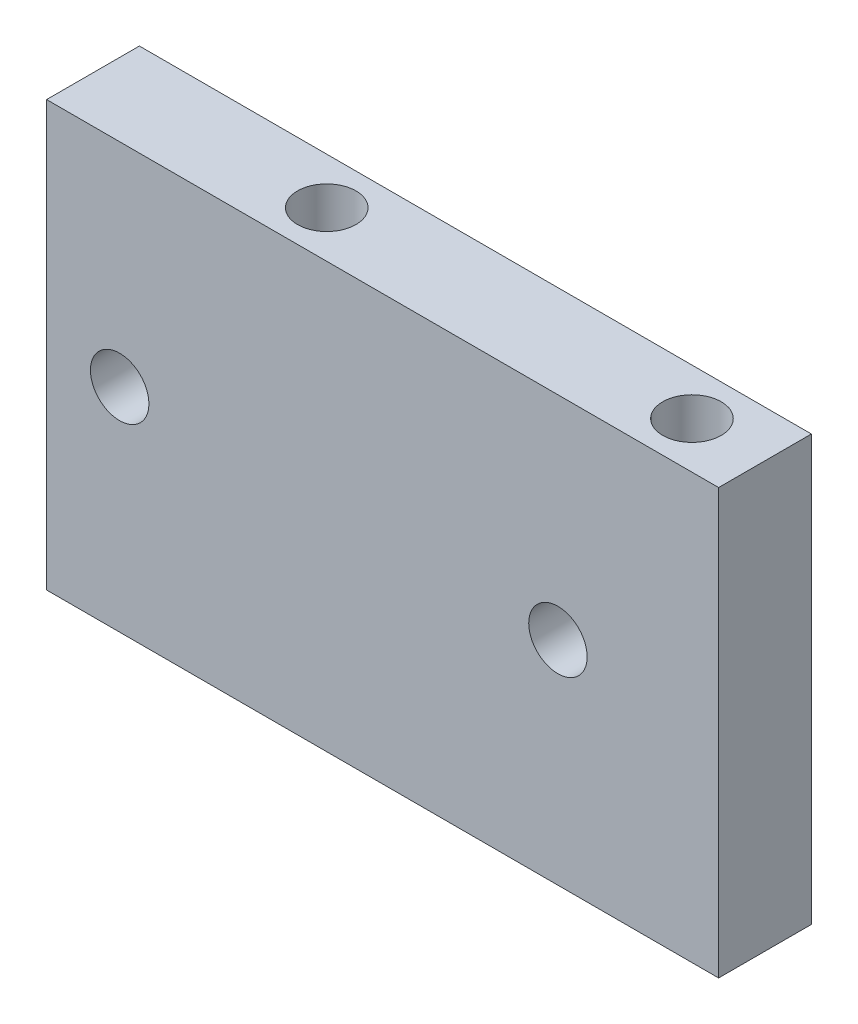
SolidWorks part; units mm, degrees
material "6061 Alloy"
ref_plane "Front Plane" through (0, 0, 0) normal (0, 0, 1) x (1, 0, 0)
ref_plane "Top Plane" through (0, 0, 0) normal (0, 1, 0) x (1, 0, 0)
ref_plane "Right Plane" through (0, 0, 0) normal (1, 0, 0) x (0, 0, -1)
sketch "Sketch1" plane through (0, 0, 0) normal (0, 0, 1) x (1, 0, 0)
  line L1 (-23, 14.5375) -> (23, 14.5375)
  line L2 (-23, 14.5375) -> (-23, -14.5375)
  line L3 (-23, -14.5375) -> (23, -14.5375)
  line L4 (23, 14.5375) -> (23, -14.5375)
  line L5 (0, -14.5375) -> (0, 14.5375) construction
  line L6 (-23, 0) -> (23, 0) construction
  point P0 (0, 0)
  dimension "D1" = 29.075
  dimension "D2" = 46
extrude "Boss-Extrude1" add sketch "Sketch1" along normal blind 6.35
sketch "Sketch2" plane through (0, 0, 0) normal (0, 0, 1) x (1, 0, 0)
  line L0 (0, 0) -> (-18, 0) construction
  line L1 (0, 0) -> (0, 8.9877) construction
  line L2 (-23, 14.5375) -> (-23, -14.5375) construction
  circle A0 centre (-18, 0) radius 2
  circle A2 centre (12, 0) radius 2
  dimension "D2" = 4
  dimension "D1" = 5
  dimension "D3" = 2
extrude "M4_DRILL" cut sketch "Sketch2" along normal up to surface (6.35 mm away) up to face at (0, 0, 6.35)
sketch "Sketch3" plane through (0, -14.5375, 0) normal (0, -1, 0) x (1, 0, 0)
  line L0 (-23, 3.175) -> (-7, 3.175) construction
  line L1 (-23, 6.35) -> (-23, 0) construction
  circle A0 centre (-7, 3.175) radius 2
  circle A1 centre (18, 3.175) radius 2
  dimension "D1" = 4
  dimension "D2" = 16
  dimension "D3" = 2
extrude "M4_DRILL2" cut sketch "Sketch3" against normal blind 8
sketch "Sketch4" plane through (0, 14.5375, 0) normal (0, 1, 0) x (1, 0, 0)
  circle A0 centre (18, -3.175) radius 2 construction
  circle A1 centre (-7, -3.175) radius 2 construction
  circle A2 centre (18, -3.175) radius 2
  circle A3 centre (-7, -3.175) radius 2
extrude "M4_DRILL3" cut sketch "Sketch4" against normal blind 8
